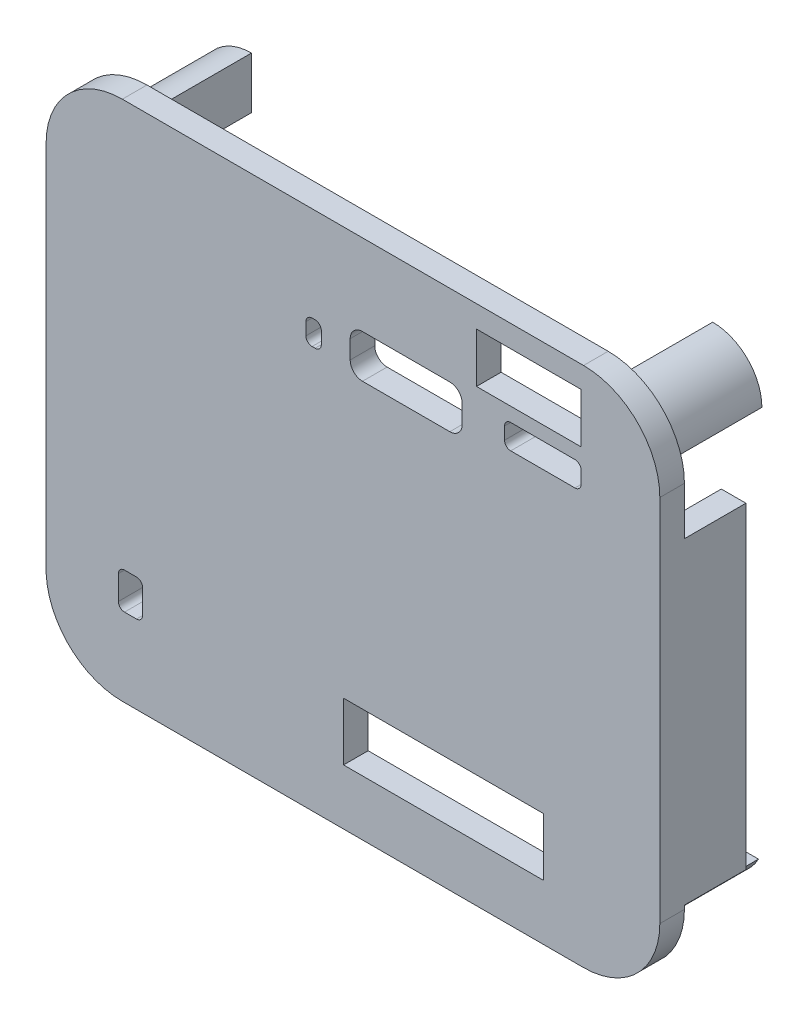
SolidWorks part; units mm, degrees
ref_plane "Front Plane" through (0, 0, 0) normal (0, 0, 1) x (1, 0, 0)
ref_plane "Top Plane" through (0, 0, 0) normal (0, 1, 0) x (1, 0, 0)
ref_plane "Right Plane" through (0, 0, 0) normal (1, 0, 0) x (0, 0, -1)
sketch "Sketch2" plane through (0, 0, 0) normal (0, 0, 1) x (1, 0, 0)
  line L0 (41.5003, -2.2) -> (3.9996, -2.2)
  line L1 (-2.1933, 3.7127) -> (-2.2, 34.0004)
  line L2 (3.9997, 40.2) -> (41.5004, 40.2)
  line L3 (47.7, 34.0003) -> (47.7, 3.9996)
  arc A0 (3.9996, -2.2) -> (-2.1933, 3.7127) centre (3.9996, 3.9995) cw
  arc A1 (-2.2, 3.9997) -> (3.9996, -2.2) centre (4.0015, 4.0015) ccw construction
  arc A2 (-2.2, 34.0004) -> (3.9997, 40.2) centre (3.9982, 34.0018) cw
  arc A3 (41.5004, 40.2) -> (47.7, 34.0003) centre (41.5004, 34.0004) cw
  arc A4 (41.5003, -2.2) -> (47.7, 3.9996) centre (41.4985, 4.0015) ccw construction
  arc A5 (47.7, 3.9996) -> (41.5003, -2.2) centre (41.5004, 3.9996) cw
extrude "Boss-Extrude1" add sketch "Sketch2" along normal blind 2
sketch "Sketch3" plane through (0, 0, 0) normal (0, 0, -1) x (-1, 0, 0)
  line L0 (-41.4985, 33.9985) -> (-41.5, 38)
  line L1 (-45.5, 34) -> (-41.4985, 33.9985)
  line L2 (-4.0015, 4.0015) -> (-4, 0)
  line L3 (0, 4) -> (-4.0015, 4.0015)
  line L4 (-4.0015, 33.9985) -> (-4.0002, 38.2)
  line L5 (0.2, 33.9998) -> (-4.0015, 33.9985)
  line L6 (-41.4985, 4.0015) -> (-45.7, 4.0002)
  line L7 (-41.4998, -0.2) -> (-41.4985, 4.0015)
  arc A0 (-41.5, 38) -> (-45.5, 34) centre (-41.4985, 33.9985) ccw
  arc A1 (-4, 0) -> (0, 4) centre (-4.0015, 4.0015) ccw
  arc A2 (-4.0002, 38.2) -> (0.2, 33.9998) centre (-4.0015, 33.9985) cw
  arc A3 (-45.7, 4.0002) -> (-41.4998, -0.2) centre (-41.4985, 4.0015) ccw
extrude "Boss-Extrude2" add sketch "Sketch3" along normal blind 8.5
sketch "Sketch4" plane through (0, 0, 0) normal (0, 0, -1) x (-1, 0, 0)
  line L0 (-47.7, 3.9996) -> (-47.7, 34.0003) construction
  line L1 (-47.7, 30.101) -> (-45.7, 30.101)
  line L2 (-47.7, 30.101) -> (-47.7, 4.2996)
  line L3 (-47.7, 4.2996) -> (-45.7, 4.2996)
  line L4 (-45.7, 30.101) -> (-45.7, 4.2996)
  line L5 (-45.7, 33.4998) -> (-45.7, 4.5003) construction
  line L6 (-45.7, 30.401) -> (-47.7, 30.401) construction
  line L7 (-47.7, 3.9996) -> (-45.7, 3.9996) construction
  dimension "D1" = 0.3
  dimension "D2" = 0.3
extrude "Boss-Extrude3" add sketch "Sketch4" along normal blind 5
sketch "Sketch5" plane through (0, 0, 0) normal (0, 0, -1) x (-1, 0, 0)
  line L0 (0.2, 4.5004) -> (0.2, 33.4997) construction
  line L1 (0.2, 22.9823) -> (1.4, 22.9823)
  line L2 (0.2, 22.9823) -> (0.2, 14.068)
  line L3 (0.2, 14.068) -> (1.4, 14.068)
  line L4 (1.4, 22.9823) -> (1.4, 14.068)
  line L5 (1.4, 11.768) -> (1.4, 25.2827) construction
  line L6 (0.2, 23.2823) -> (1.4, 23.2823) construction
  line L7 (1.4, 13.768) -> (0.2, 13.768) construction
  dimension "D1" = 0.3
  dimension "D2" = 0.3
extrude "Boss-Extrude4" add sketch "Sketch5" along normal blind 5.3
sketch "Sketch6" plane through (0, 0, 0) normal (0, 0, -1) x (-1, 0, 0)
  line L1 (-38.2624, 7.0162) -> (-21.9848, 7.0162)
  line L2 (-38.2624, 7.0162) -> (-38.2624, 2.3138)
  line L3 (-38.2624, 2.3138) -> (-21.9848, 2.3138)
  line L4 (-21.9848, 7.0162) -> (-21.9848, 2.3138)
  line L5 (-41.3098, 38.4131) -> (-32.7951, 38.4131)
  line L6 (-41.3098, 38.4131) -> (-41.3098, 34.3696)
  line L7 (-41.3098, 34.3696) -> (-32.7951, 34.3696)
  line L8 (-32.7951, 38.4131) -> (-32.7951, 34.3696)
  line L9 (-31.625, 33.6) -> (-22.525, 33.6)
  line L10 (-31.625, 33.6) -> (-31.625, 30.1)
  line L11 (-31.625, 30.1) -> (-22.525, 30.1)
  line L12 (-22.525, 33.6) -> (-22.525, 30.1)
  line L13 (-41.3, 33.225) -> (-35.075, 33.225)
  line L14 (-41.3, 33.225) -> (-41.3, 31.225)
  line L15 (-41.3, 31.225) -> (-35.075, 31.225)
  line L16 (-35.075, 33.225) -> (-35.075, 31.225)
  line L17 (-5.65, 7.1297) -> (-3.675, 7.1297)
  line L18 (-5.65, 7.1297) -> (-5.65, 4.1708)
  line L19 (-5.65, 4.1708) -> (-3.675, 4.1708)
  line L20 (-3.675, 7.1297) -> (-3.675, 4.1708)
  line L21 (-20.175, 32.5) -> (-18.925, 32.5)
  line L22 (-20.175, 32.5) -> (-20.175, 30.5)
  line L23 (-20.175, 30.5) -> (-18.925, 30.5)
  line L24 (-18.925, 32.5) -> (-18.925, 30.5)
extrude "Cut-Extrude1" cut sketch "Sketch6" against normal through all
fillet "Fillet1" radius 1 13 edges at (2.0007, 4.0007, 0) (4.0007, 2.0007, 0) (4.0008, 36.0993, 0) (1.9007, 33.9992, 0) (43.4993, 33.9993, 0) (45.7, 17.2003, 0) (22.525, 33.6, 1) (22.525, 30.1, 1) (31.625, 30.1, 1) (31.625, 33.6, 1) (41.4992, 1.9007, 0) (-1.4, 18.5252, 0) (-0.2, 18.5252, 0)
fillet "Fillet2" radius 0.5 12 edges at (35.075, 31.225, 1) (35.075, 33.225, 1) (41.3, 33.225, 1) (41.3, 31.225, 1) (18.925, 30.5, 1) (20.175, 30.5, 1) (20.175, 32.5, 1) (18.925, 32.5, 1) (3.675, 7.1297, 1) (3.675, 4.1708, 0.7785) (5.65, 4.1708, 1) (5.65, 7.1297, 1)
sketch "Sketch7" plane through (0, 0, -8.5) normal (0, 0, -1) x (-1, 0, 0)
  line L0 (-40.4985, 4.0018) -> (-45.7, 4.0002) construction
  line L1 (-45.9255, 2.0515) -> (-39.6129, 2.0515)
  line L2 (-45.9255, 2.0515) -> (-45.9255, 4.002)
  line L3 (-45.9255, 4.002) -> (-39.6129, 4.002)
  line L4 (-39.6129, 2.0515) -> (-39.6129, 4.002)
extrude "Cut-Extrude2" cut sketch "Sketch7" against normal up to surface (8.5 mm away) up to face at (38.1875, 32.225, 0)
